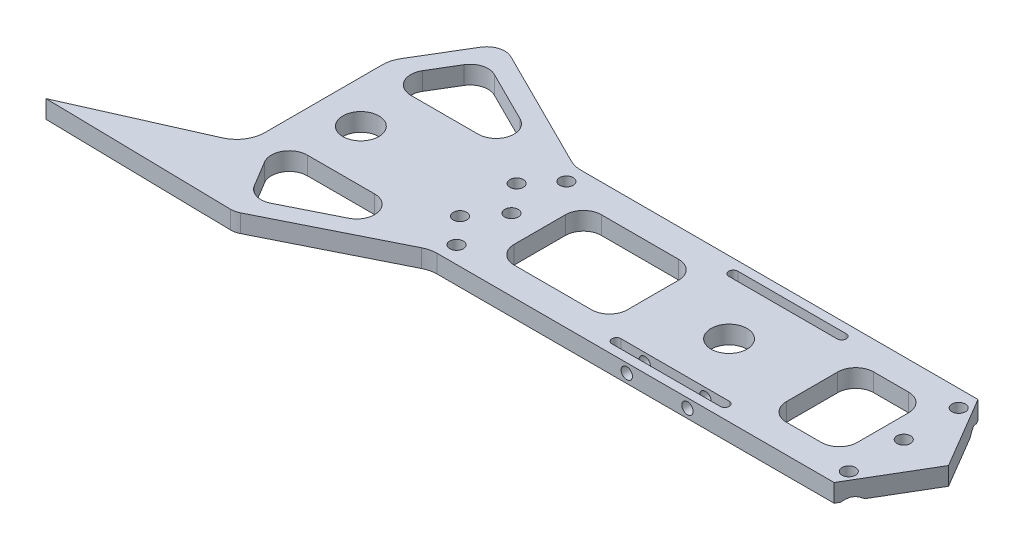
SolidWorks part; units mm, degrees
material "AISI 1020"
ref_plane "Alzado" through (0, 0, 0) normal (0, 0, 1) x (1, 0, 0)
ref_plane "Planta" through (0, 0, 0) normal (0, 1, 0) x (1, 0, 0)
ref_plane "Vista lateral" through (0, 0, 0) normal (1, 0, 0) x (0, 0, -1)
sketch "Croquis1" plane through (0, 0, 0) normal (0, 1, 0) x (1, 0, 0)
  line L0 (37.5, -25.4) -> (52.5, 0)
  line L3 (-45.9466, -25.4) -> (37.5, -25.4) construction
  line L4 (37.5, 25.4) -> (37.5, -25.4) construction
  line L5 (52.5, 0) -> (37.5, 25.4)
  line L6 (0, 0) -> (37.5, 0) construction
  line L11 (0, 0) -> (0, -19.05) construction
  line L12 (-19.05, 19.05) -> (19.05, 19.05) construction
  line L13 (-19.05, 19.05) -> (-19.05, -19.05) construction
  line L14 (-19.05, -19.05) -> (19.05, -19.05) construction
  line L15 (19.05, 19.05) -> (19.05, -19.05) construction
  line L16 (37.5, 25.4) -> (-105, 25.4)
  line L20 (-105, -25.4) -> (37.5, -25.4)
  line L21 (0, 0) -> (-170, 0) construction
  line L24 (-3.261, -52.3986) -> (59.3724, -56.2966) construction
  line L38 (-105, -25.4) -> (-105, 25.4) construction
  line L41 (-105, -25.4) -> (-149.7468, -47.7317)
  line L42 (-158.0248, -45.3215) -> (-170, -25.4) construction
  line L43 (-170, -25.4) -> (-170, 25.4)
  line L44 (-170, 25.4) -> (-158.0248, 45.3215)
  line L45 (-149.7468, 47.7317) -> (-105, 25.4)
  line L46 (-155, -50.3534) -> (-155, 50.3534) construction
  line L47 (-170, 25.4) -> (-105, 25.4) construction
  line L48 (-105, -25.4) -> (-170, -25.4) construction
  line L49 (-170, -25.4) -> (-219.0316, -47.147)
  line L50 (-219.0316, -47.147) -> (-152.7022, -48.3989)
  line L51 (-173.3511, 48.4) -> (-113.9016, 48.4) construction
  line L52 (-129.0451, 30.3033) -> (-147.3292, 39.4283)
  line L53 (-155.6072, 37.0181) -> (-161.0924, 27.8931)
  line L54 (-155.65, 18.2716) -> (-131.8807, 18.2716)
  line L55 (-182.7394, 6.35) -> (-126.5741, 6.35) construction
  line L56 (-162, 48.4) -> (-162, -3.791) construction
  line L57 (-129.0451, -30.3033) -> (-147.3292, -39.4283)
  line L58 (-155.6072, -37.0181) -> (-161.0924, -27.8931)
  line L59 (-155.65, -18.2716) -> (-131.8807, -18.2716)
  line L60 (-135, 6.35) -> (-115, 6.35) construction
  line L61 (-115, -6.35) -> (-135, -6.35) construction
  circle A0 centre (0, 0) radius 6.35 construction
  circle A1 centre (0, 0) radius 52.5 construction
  circle A11 centre (-155, 0) radius 6.35
  circle A12 centre (-155, 0) radius 44.45 construction
  arc A13 (-149.7468, -47.7317) -> (-158.0248, -45.3215) centre (-152.5824, -42.05) cw construction
  arc A14 (-158.0248, 45.3215) -> (-149.7468, 47.7317) centre (-152.5824, 42.05) cw
  arc A15 (-152.7022, -48.3989) -> (-149.7468, -47.7317) centre (-152.5824, -42.05) ccw
  arc A16 (-129.0451, 30.3033) -> (-131.8807, 18.2716) centre (-131.8807, 24.6216) cw
  arc A17 (-161.0924, 27.8931) -> (-155.65, 18.2716) centre (-155.65, 24.6216) ccw
  arc A18 (-147.3292, 39.4283) -> (-155.6072, 37.0181) centre (-150.1648, 33.7466) ccw
  arc A19 (-129.0451, -30.3033) -> (-131.8807, -18.2716) centre (-131.8807, -24.6216) ccw
  arc A20 (-147.3292, -39.4283) -> (-155.6072, -37.0181) centre (-150.1648, -33.7466) cw
  arc A21 (-161.0924, -27.8931) -> (-155.65, -18.2716) centre (-155.65, -24.6216) cw
  arc A22 (-135, 6.35) -> (-135, -6.35) centre (-135, 0) ccw construction
  arc A23 (-115, -6.35) -> (-115, 6.35) centre (-115, 0) ccw construction
  circle A32 centre (-25, 0) radius 50.8 construction
  circle A33 centre (-25, 0) radius 6.35
  point P19 (19.05, 0)
  point P20 (-170, 0)
  dimension "D1" = 12.7
  dimension "D2" = 105
  dimension "D7" = 6.35
  dimension "D10" = 23
  dimension "D11" = 25
  dimension "D9" = 15
  dimension "D15" = 20
  dimension "D3" = 50
  dimension "D4" = 88.9
  dimension "D12" = 12.7
  dimension "D13" = 6.35
  dimension "D18" = 6.35
  dimension "D20" = 101.6
  dimension "D5" = 50.8
  dimension "D6" = 15
  dimension "D8" = 38.1
  dimension "D14" = 8
  dimension "D16" = 10
  dimension "D17" = 105
  dimension "D19" = 80
extrude "Saliente-Extruir1" add sketch "Croquis1" along normal blind 6.35
sketch "Croquis4" plane through (0, 6.35, 0) normal (0, 1, 0) x (1, 0, 0)
  line L0 (-105, -25.4) -> (37.5, -25.4) construction
  line L1 (-101.825, -25.4) -> (-105, -25.4) construction
  line L2 (-101.825, -25.4) -> (-101.825, 25.4) construction
  line L3 (-101.825, 25.4) -> (-105, 25.4) construction
  line L4 (-105, -25.4) -> (-105, 25.4) construction
  line L5 (37.5, 25.4) -> (-105, 25.4) construction
  line L6 (37.5, -25.4) -> (34.325, -25.4)
  line L7 (37.5, -25.4) -> (37.5, 25.4)
  line L8 (37.5, 25.4) -> (34.325, 25.4)
  line L9 (34.325, -25.4) -> (34.325, 25.4)
  dimension "D1" = 3.175
extrude "Cortar-Extruir1" [suppressed] cut sketch "Croquis4" along normal blind 3.175 from surface
fillet "Redondeo1" radius 10 4 edges at (-170, 3.175, -25.4) (-170, 3.175, 25.4) (-105, 3.175, -25.4) (-105, 3.175, 25.4)
sketch "Croquis5" plane through (0, 0, 0) normal (0, -1, 0) x (1, 0, 0)
  line L0 (-44.125, 22.225) -> (-5.875, 22.225)
  line L1 (-5.875, 19.05) -> (-44.125, 19.05)
  line L2 (-19.05, 19.05) -> (19.05, 19.05) construction
  line L3 (-25, 0) -> (-25, 19.05) construction
  line L4 (-19.05, 0) -> (37.5, 0) construction
  line L5 (0, 0) -> (-170, 0) construction
  line L6 (-5.875, -19.05) -> (-44.125, -19.05)
  line L7 (-44.125, -22.225) -> (-5.875, -22.225)
  arc A0 (-44.125, 22.225) -> (-44.125, 19.05) centre (-44.125, 20.6375) ccw
  arc A1 (-5.875, 19.05) -> (-5.875, 22.225) centre (-5.875, 20.6375) ccw
  arc A2 (-5.875, -19.05) -> (-5.875, -22.225) centre (-5.875, -20.6375) cw
  arc A3 (-44.125, -22.225) -> (-44.125, -19.05) centre (-44.125, -20.6375) cw
  dimension "D1" = 3.175
  dimension "D2" = 38.25
extrude "Cortar-Extruir2" cut sketch "Croquis5" against normal through all
sketch "Croquis6" plane through (0, 0, 0) normal (0, -1, 0) x (1, 0, 0)
  line L1 (-85.475, 15.4) -> (-58.175, 15.4)
  line L2 (-91.825, 9.05) -> (-91.825, -9.05)
  line L3 (-85.475, -15.4) -> (-58.175, -15.4)
  line L4 (-51.825, 9.05) -> (-51.825, -9.05)
  line L5 (10.675, 15.4) -> (22.975, 15.4)
  line L6 (4.325, 9.05) -> (4.325, -9.05)
  line L7 (10.675, -15.4) -> (22.975, -15.4)
  line L8 (29.325, 9.05) -> (29.325, -9.05)
  line L9 (34.325, 25.4) -> (34.325, -25.4) construction
  line L10 (37.5, -25.4) -> (-102.6433, -25.4) construction
  line L11 (-102.6433, 25.4) -> (37.5, 25.4) construction
  line L12 (-170, -22.6257) -> (-170, 18.8958) construction
  arc A0 (22.975, -15.4) -> (29.325, -9.05) centre (22.975, -9.05) ccw
  arc A1 (22.975, 15.4) -> (29.325, 9.05) centre (22.975, 9.05) cw
  arc A2 (10.675, 15.4) -> (4.325, 9.05) centre (10.675, 9.05) ccw
  arc A3 (4.325, -9.05) -> (10.675, -15.4) centre (10.675, -9.05) ccw
  arc A4 (-58.175, -15.4) -> (-51.825, -9.05) centre (-58.175, -9.05) ccw
  arc A5 (-58.175, 15.4) -> (-51.825, 9.05) centre (-58.175, 9.05) cw
  arc A6 (-91.825, -9.05) -> (-85.475, -15.4) centre (-85.475, -9.05) ccw
  arc A7 (-85.475, 15.4) -> (-91.825, 9.05) centre (-85.475, 9.05) ccw
  point P12 (29.325, -15.4)
  dimension "D1" = 6.35
  dimension "D2" = 78.175
  dimension "D3" = 40
  dimension "D4" = 10
  dimension "D5" = 10
  dimension "D6" = 25
  dimension "D7" = 5
extrude "Cortar-Extruir3" cut sketch "Croquis6" against normal through all
sketch "Croquis7" plane through (0, 0, 0) normal (0, -1, 0) x (1, 0, 0)
  line L0 (-101.825, -25.4) -> (-101.825, 25.4) construction
  line L1 (37.5, -25.4) -> (-102.6433, -25.4) construction
  line L2 (-102.6433, 25.4) -> (37.5, 25.4) construction
  line L3 (-32.5716, -25.4) -> (-32.5716, 25.4) construction
  line L4 (36.6817, -25.4) -> (36.6817, 25.4) construction
  line L6 (37.5, -25.4) -> (-102.6433, -25.4) construction
  line L7 (-102.6433, 25.4) -> (37.5, 25.4) construction
  line L8 (-91.825, 9.05) -> (-91.825, -9.05) construction
  circle A0 centre (-101.825, 0) radius 2.3813
  circle A1 centre (-101.825, 19.4) radius 2.3813
  circle A2 centre (-101.825, -19.4) radius 2.3813
  circle A3 centre (36.6817, -19.4) radius 2.3813
  circle A4 centre (36.6817, 19.4) radius 2.3813
  circle A5 centre (36.6817, 0) radius 2.3812
  dimension "D1" = 4.7625
  dimension "D2" = 6
  dimension "D3" = 6
  dimension "D4" = 10
extrude "Cortar-Extruir4" cut sketch "Croquis7" against normal through all
sketch "Croquis8" plane through (0, 0, 0) normal (0, -1, 0) x (1, 0, 0)
  line L0 (0, 0) -> (-110, 0) construction
  line L1 (-110, 10) -> (-110, -10)
  circle A0 centre (-110, -10) radius 2.3813
  circle A1 centre (-110, 10) radius 2.3813
  dimension "D1" = 20
  dimension "D2" = 4.7625
  dimension "D3" = 110
extrude "Cortar-Extruir5" cut sketch "Croquis8" against normal through all contours A1 | A0 region at (-111.6362, 0, 11.6362)
sketch "Croquis9" plane through (0, 0, 25.4) normal (0, 0, 1) x (1, 0, 0)
  line L0 (37.5, 3.175) -> (-102.6433, 3.175) construction
  line L1 (37.5, 6.35) -> (37.5, 0) construction
  line L2 (-102.6433, 6.35) -> (-102.6433, 0) construction
  circle A0 centre (-14.2875, 3.175) radius 2
  circle A1 centre (-35.7125, 3.175) radius 2
  dimension "D3" = 4
  dimension "D1" = 10
  dimension "D2" = 10
extrude "Cortar-Extruir6" cut sketch "Croquis9" against normal blind 15
chamfer "Chaflán1" distance 2.5 angle 45 6 edges at (36.6817, 0, 21.7813) (36.6817, 0, -17.0188) (36.6817, 0, 2.3812) (-101.825, 0, 17.0188) (-101.825, 0, -2.3813) (-101.825, 0, -21.7813)
